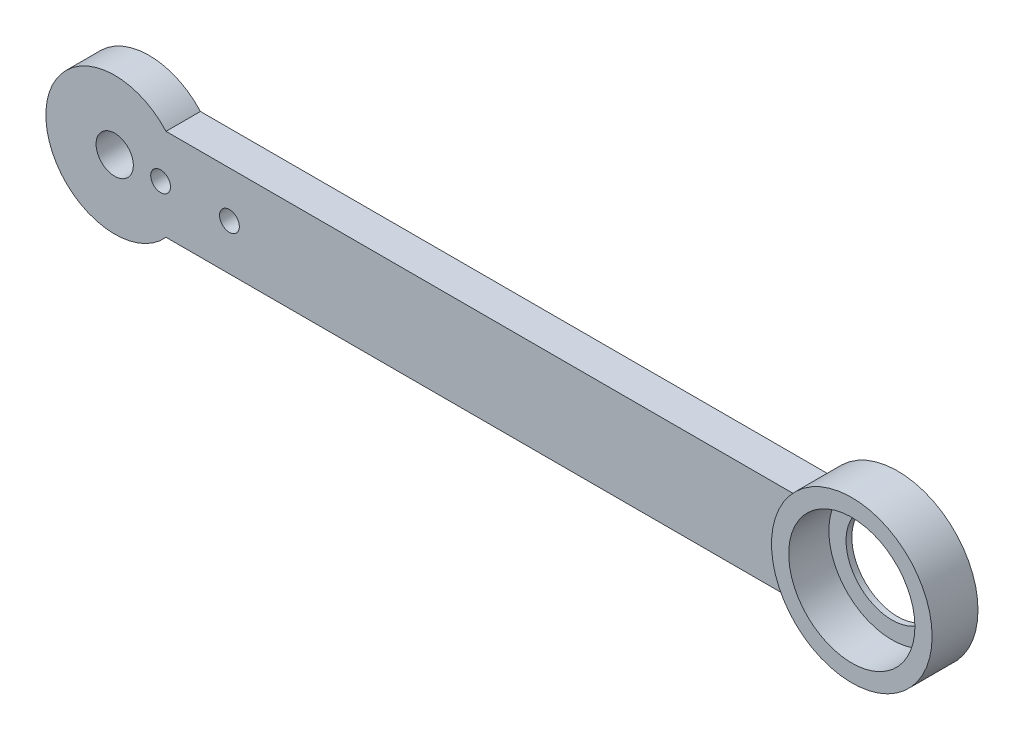
SolidWorks part; units mm, degrees
ref_plane "Front Plane" through (0, 0, 0) normal (0, 0, 1) x (1, 0, 0)
ref_plane "Top Plane" through (0, 0, 0) normal (0, 1, 0) x (1, 0, 0)
ref_plane "Right Plane" through (0, 0, 0) normal (1, 0, 0) x (0, 0, -1)
sketch "Sketch1" plane through (0, 0, 0) normal (0, 0, 1) x (1, 0, 0)
  line L0 (0, -8) -> (130, -8)
  line L1 (130, -8) -> (130, 8)
  line L2 (130, 8) -> (0, 8)
  line L3 (0, 8) -> (0, -8)
extrude "Boss-Extrude1" add sketch "Sketch1" along normal blind 6 from offset 3
sketch "Sketch2" plane through (0, 0, 0) normal (0, 0, 1) x (1, 0, 0)
  circle A0 centre (0, 0) radius 12
extrude "Boss-Extrude2" add sketch "Sketch2" along normal blind 6 from offset 3
sketch "Sketch3" plane through (0, 0, 0) normal (0, 0, 1) x (1, 0, 0)
  circle A0 centre (130, 0) radius 14
extrude "Boss-Extrude3" add sketch "Sketch3" along normal blind 6 from offset 3
sketch "Sketch4" plane through (0, 0, 0) normal (0, 0, 1) x (1, 0, 0)
  circle A0 centre (130, 0) radius 14
extrude "Boss-Extrude4" add sketch "Sketch4" along normal blind 8 from offset 2.5
sketch "Sketch5" plane through (0, 0, 0) normal (0, 0, 1) x (1, 0, 0)
  circle A0 centre (0, 0) radius 3.25
extrude "Cut-Extrude1" cut sketch "Sketch5" against normal through all and the other way through all
sketch "Sketch6" plane through (0, 0, 0) normal (0, 0, 1) x (1, 0, 0)
  circle A0 centre (8, 0) radius 1.725
  circle A1 centre (20, 0) radius 1.725
extrude "Cut-Extrude2" cut sketch "Sketch6" against normal through all and the other way through all
sketch "Sketch7" plane through (0, 0, 0) normal (0, 0, 1) x (1, 0, 0)
  circle A0 centre (8, 0) radius 2.9
extrude "Cut-Extrude3" cut sketch "Sketch7" along normal blind 2.2 from offset 3
sketch "Sketch8" plane through (0, 0, 0) normal (0, 0, 1) x (1, 0, 0)
  circle A0 centre (20, 0) radius 2.9
extrude "Cut-Extrude4" cut sketch "Sketch8" along normal blind 2.2 from offset 3
sketch "Sketch9" plane through (0, 0, 0) normal (0, 0, 1) x (1, 0, 0)
  circle A0 centre (130, 0) radius 11
extrude "Cut-Extrude5" cut sketch "Sketch9" along normal blind 7 from offset 3.5
sketch "Sketch10" plane through (0, 0, 0) normal (0, 0, 1) x (1, 0, 0)
  circle A0 centre (130, 0) radius 8
extrude "Cut-Extrude6" cut sketch "Sketch10" against normal through all and the other way through all
